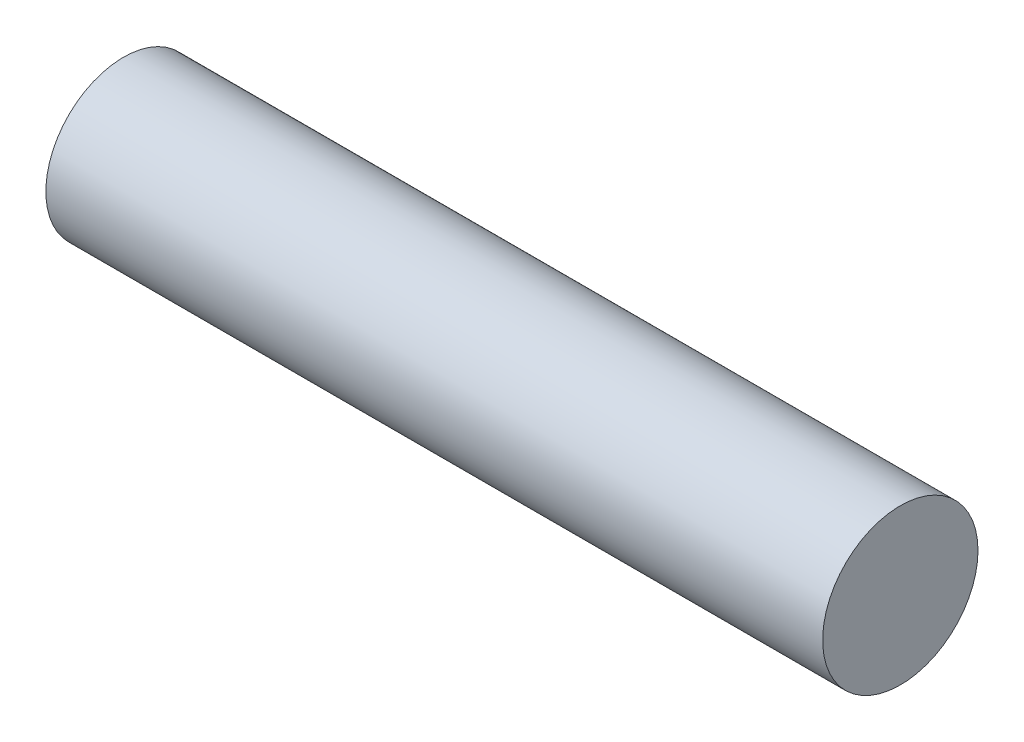
SolidWorks part; units mm, degrees
ref_plane "Front Plane" through (0, 0, 0) normal (0, 0, 1) x (1, 0, 0)
ref_plane "Top Plane" through (0, 0, 0) normal (0, 1, 0) x (1, 0, 0)
ref_plane "Right Plane" through (0, 0, 0) normal (1, 0, 0) x (0, 0, -1)
sketch "Sketch2" plane through (0, 0, 0) normal (0, 1, 0) x (1, 0, 0)
  line L0 (0, 0) -> (-381, 0) construction
  line L1 (0, 0) -> (0, 38.1)
  line L2 (0, 38.1) -> (-381, 38.1)
  line L3 (-381, 38.1) -> (-381, 0)
  line L4 (0, 0) -> (-381, 0)
  dimension "D1" = 381
  dimension "D2" = 381
  dimension "D3" = 38.1
revolve "Revolve1" add sketch "Sketch2" angle 360 about L0
